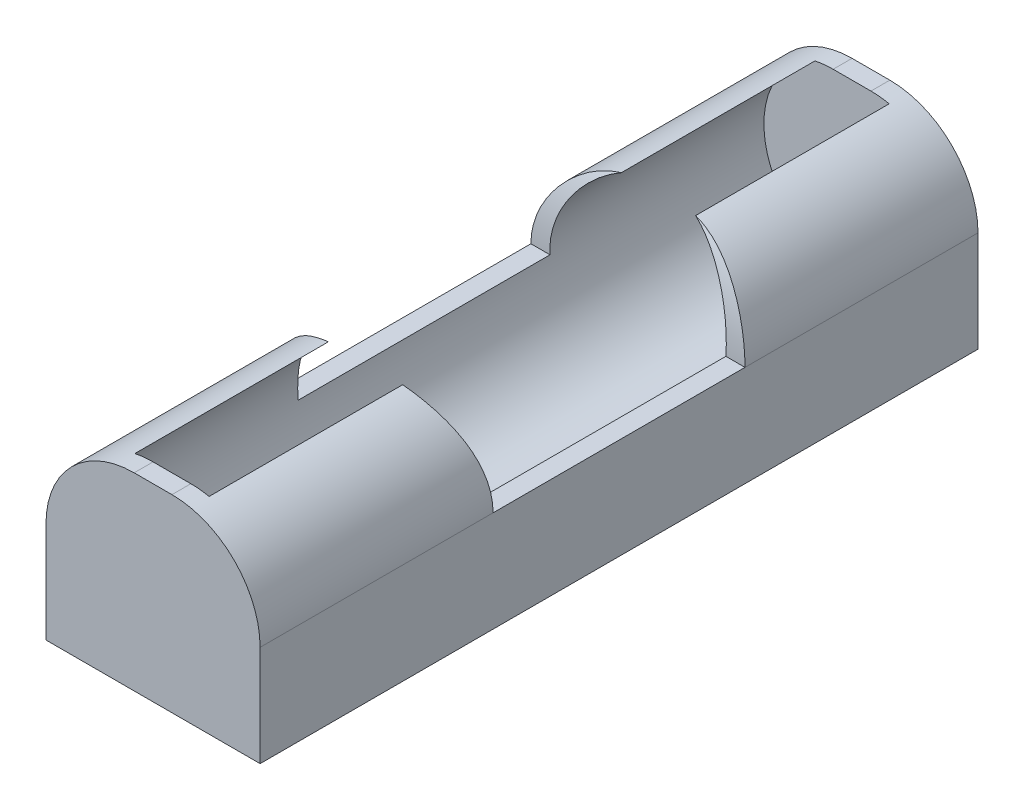
SolidWorks part; units mm, degrees
ref_plane "Front Plane" through (0, 0, 0) normal (0, 0, 1) x (1, 0, 0)
ref_plane "Top Plane" through (0, 0, 0) normal (0, 1, 0) x (1, 0, 0)
ref_plane "Right Plane" through (0, 0, 0) normal (1, 0, 0) x (0, 0, -1)
sketch "Sketch1" plane through (0, 0, 0) normal (0, 1, 0) x (1, 0, 0)
  line L0 (0, 0) -> (0, -55.5)
  line L2 (47, -55.5) -> (47, 0)
  line L3 (47, 0) -> (0, 0)
  line L5 (0, -55.5) -> (47, -55.5)
extrude "Boss-Extrude1" add sketch "Sketch1" along normal blind 15
sketch "Sketch2" plane through (0, 0, 55.5) normal (0, 0, 1) x (1, 0, 0)
  line L0 (0, 15) -> (47, 15) construction
  line L1 (0, 15) -> (47, 15)
  line L2 (0, 15) -> (0, 0)
  line L3 (0, 0) -> (47, 0)
  line L4 (47, 15) -> (47, 0)
  line L5 (0, 15) -> (0, 0) construction
  circle A0 centre (8.5, 8.5) radius 7
  circle A1 centre (23.5, 8.5) radius 7
  circle A2 centre (38.5, 8.5) radius 7
extrude "Cut-Extrude4" cut sketch "Sketch2" against normal blind 54 contours L1 A0 | L1 A1 | L1 A2 region at (8.5, 8.4232, 55.5) region at (23.5, 8.4232, 55.5) region at (38.5, 8.4232, 55.5)
fillet "Fillet1" radius 7 1 edges at (47, 15, 27.75) type face fillet first side face at (23.5, 15, 28.3125) second side face at (47, 7.5, 27.75)
fillet "Fillet2" radius 7 1 edges at (0, 15, 27.75) type face fillet first side face at (19.986, 15, 24.4286) second side face at (0, 7.5, 27.75)
sketch "Sketch3" plane through (0, 0, 55.5) normal (0, 0, 1) x (1, 0, 0)
  line L0 (30.5, 8.5) -> (30.5, 15)
  line L1 (26.0981, 15) -> (35.9019, 15) construction
  line L3 (26.0981, 15) -> (26.0981, 8.5)
  line L4 (26.0981, 8.5) -> (30.5, 8.5)
  line L5 (35.9019, 8.5) -> (35.9019, 15)
  line L6 (35.9019, 15) -> (31.5, 15)
  line L7 (31.5, 8.5) -> (31.5, 15)
  line L8 (30.5, 15) -> (26.0981, 15)
  line L9 (31.5, 8.5) -> (35.9019, 8.5)
  line L11 (15.5, 8.5) -> (11.0981, 8.5)
  line L12 (16.5, 15) -> (20.9019, 15)
  line L13 (15.5, 8.5) -> (15.5, 15)
  line L14 (11.0981, 15) -> (15.5, 15)
  line L15 (11.0981, 8.5) -> (11.0981, 15)
  line L16 (20.9019, 8.5) -> (16.5, 8.5)
  line L17 (20.9019, 15) -> (20.9019, 8.5)
  line L18 (16.5, 8.5) -> (16.5, 15)
  arc A1 (20.9019, 15) -> (26.0981, 15) centre (23.5, 8.5) ccw construction
  arc A2 (35.9019, 15) -> (41.4494, 14.8483) centre (38.5, 8.5) ccw construction
extrude "Cut-Extrude5" cut sketch "Sketch3" against normal blind 54
sketch "Sketch4" plane through (0, 0, 55.5) normal (0, 0, 1) x (1, 0, 0)
  line L0 (15.5, 15) -> (15.5, 14)
  line L2 (15.5, 14) -> (16.5, 14)
  line L3 (16.5, 15) -> (16.5, 8.5) construction
  line L4 (16.5, 14) -> (16.5, 15)
  line L5 (16.5, 15) -> (15.5, 15)
  line L6 (16.5, 15) -> (30.5, 15) construction
  line L7 (23.5, 15) -> (23.5, 12.7021)
  line L8 (30.5, 14) -> (30.5, 15)
  line L9 (31.5, 14) -> (30.5, 14)
  line L10 (31.5, 15) -> (31.5, 14)
  line L11 (30.5, 15) -> (31.5, 15)
  line M7 (16.5, 15) -> (15.5, 15)
  line M8 (15.5, 15) -> (15.5, 8.5)
  line M16 (31.5, 8.5) -> (31.5, 15)
  line M17 (31.5, 15) -> (30.5, 15)
  line M18 (30.5, 15) -> (30.5, 8.5)
  line M20 (16.5, 8.5) -> (16.5, 15)
extrude "Cut-Extrude6" cut sketch "Sketch4" against normal blind 54 contours L2 M8 M20 M7 | L9 M16 M17 M18 region at (16, 14.5, 55.5) region at (31, 14.5, 55.5)
sketch "Sketch5" plane through (15.5, 0, 0) normal (-1, 0, 0) x (0, 0, 1)
  line L0 (6.5, 14) -> (50.5, 14)
  line L1 (1.5, 14) -> (55.5, 14) construction
  line L4 (6.5, 14) -> (16.5, 7)
  line L5 (28.5, 14) -> (28.5, 8.5) construction
  line L6 (1.5, 8.5) -> (55.5, 8.5) construction
  line L9 (50.5, 14) -> (40.5, 7)
  line L10 (40.5, 7) -> (16.5, 7)
extrude "Cut-Extrude7" cut sketch "Sketch5" against normal blind 20
extrude "Cut-Extrude8" cut sketch "Sketch5<2>" along normal blind 5
sketch "Sketch5<2>" plane through (15.5, 0, 0) normal (-1, 0, 0) x (0, 0, 1) same geometry as "Sketch5"
sketch "Sketch6" plane through (0, 0, 55.5) normal (0, 0, 1) x (1, 0, 0)
  line L0 (0, 0) -> (47, 0)
  line L1 (47, 0) -> (47, 8)
  line L2 (40, 15) -> (7, 15)
  line L3 (0, 8) -> (0, 0)
  arc A0 (47, 8) -> (40, 15) centre (40, 8) ccw
  arc A2 (7, 15) -> (0, 8) centre (7, 8) ccw
extrude "Boss-Extrude3" add sketch "Sketch6" along normal blind 1.5
sketch "Sketch7" plane through (0, 0, 57) normal (0, 0, 1) x (1, 0, 0)
  line L1 (16, 8) -> (16, 15)
  line L2 (40, 15) -> (7, 15) construction
  line L3 (16, 8) -> (16, 0)
  line L4 (0, 0) -> (47, 0) construction
  line L5 (16, 0) -> (47, 0)
  line L6 (47, 0) -> (47, 15)
  line L7 (47, 15) -> (16, 15)
extrude "Cut-Extrude9" cut sketch "Sketch7" against normal blind 57
mirror "Mirror1" about plane through (16, 8, 0) normal (-1, 0, 0) of bodies 112
sketch "Sketch8" plane through (0, 0, 55.5) normal (0, 0, -1) x (-1, 0, 0)
  line L0 (-8.5, 8.5) -> (-8.5, 1.5)
  line L1 (-8.5, 8.5) -> (-8.5, 15)
  line L2 (-25, 15) -> (-7, 15) construction
  arc A0 (-15.5, 8.5) -> (-5.5506, 14.8483) centre (-8.5, 8.5) ccw construction
sketch "Sketch10" plane through (0, 15, 0) normal (0, 1, 0) x (1, 0, 0)
  line L0 (8.5, -55.5) -> (8.5, -57)
  line L1 (25, -57) -> (7, -57) construction
sketch "Sketch11" plane through (0, 0, 57) normal (0, 0, 1) x (1, 0, 0)
  line L0 (8.5, 15) -> (8.5, 0)
  line L1 (0, 0) -> (32, 0) construction
  line L2 (8.5, 0) -> (32, 0)
  line L3 (32, 0) -> (32, 15)
  line L4 (32, 15) -> (8.5, 15)
extrude "Cut-Extrude10" cut sketch "Sketch11" against normal through all
sketch "Sketch12" plane through (0, 0, 57) normal (0, 0, 1) x (1, 0, 0)
  line L1 (15.3265, 15) -> (15.3265, 3.6164)
  line L2 (15.3265, 3.6164) -> (22.6127, 3.6164)
  line L3 (22.6127, 3.6164) -> (22.6127, 15)
  line L4 (22.6127, 15) -> (15.3265, 15)
extrude "Boss-Extrude4" add sketch "Sketch12" along normal blind 10 separate body
mirror "Mirror2" about plane through (8.5, 15, 0) normal (-1, 0, 0) of bodies 114
delete or keep bodies "Body-Delete/Keep 1" type delete bodies bodies 115
combine bodies "Combine1" operation type add bodies to combine 114 116
sketch "Sketch13" plane through (17, 0, 0) normal (1, 0, 0) x (0, 0, -1)
  line L1 (-38.5, 8) -> (-18.5, 8)
  line L4 (-38.5, 22.8552) -> (-18.5, 22.8552)
  line L6 (-38.5, 22.8552) -> (-50.5, 22.8552)
  line L7 (-18.5, 22.8552) -> (-6.5, 22.8552)
  arc A0 (-38.5, 8) -> (-50.5, 22.8552) centre (-53.6949, 8) ccw
  arc A1 (-6.5, 22.8552) -> (-18.5, 8) centre (-3.3051, 8) ccw
extrude "Cut-Extrude11" cut sketch "Sketch13" against normal through all
